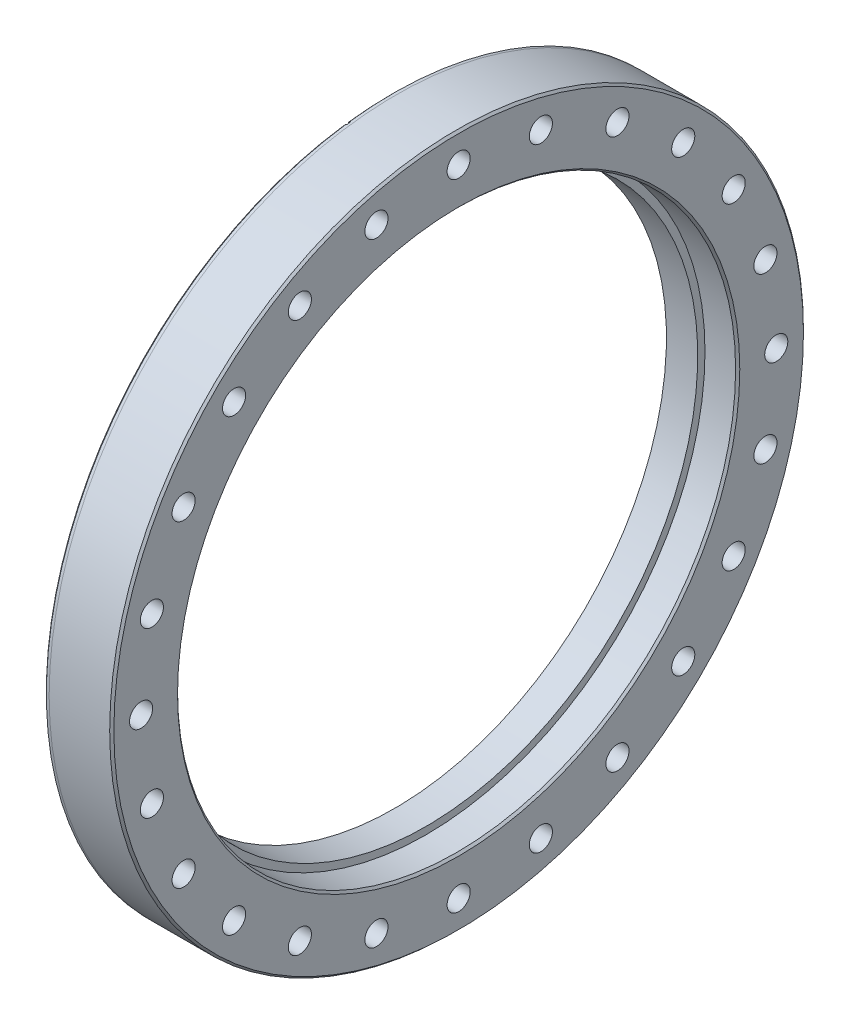
SolidWorks part; units mm, degrees
ref_plane "Front Plane" through (0, 0, 0) normal (0, 0, 1) x (1, 0, 0)
ref_plane "Top Plane" through (0, 0, 0) normal (0, 1, 0) x (1, 0, 0)
ref_plane "Right Plane" through (0, 0, 0) normal (1, 0, 0) x (0, 0, -1)
sketch "Sketch1" plane through (0, 0, 0) normal (0, 0, 1) x (1, 0, 0)
  line L0 (255.9008, 390.4907) -> (255.9008, 381.2451)
  line L1 (267.3308, 383.8867) -> (267.3308, 381.2451)
  line L2 (254.6308, 407.8872) -> (254.6308, 393.1548)
  line L3 (234.5105, 282.0327) -> (295.2534, 282.0327) construction
  line L14 (254.6308, 407.8872) -> (255.3928, 408.6492)
  line L25 (279.2688, 384.6487) -> (278.5068, 383.8867)
  line L27 (256.2619, 393.1577) -> (255.2912, 390.4907)
  line L36 (279.2688, 407.8897) -> (279.2688, 384.6487)
  line L48 (255.9008, 381.2451) -> (267.3308, 381.2451)
  line L49 (278.5068, 383.8867) -> (267.3308, 383.8867)
  line L50 (278.5068, 408.6517) -> (279.2688, 407.8897)
  line L51 (255.9008, 390.4907) -> (255.2912, 390.4907)
  line L52 (255.5972, 393.1577) -> (254.6308, 393.1548)
  line L53 (256.2619, 393.1577) -> (255.5972, 393.1577)
  line L54 (255.3928, 408.6492) -> (256.4093, 408.6517)
  line L55 (256.4093, 408.6517) -> (278.5068, 408.6517)
  dimension "D1" = 126.619
revolve "Revolve1" add sketch "Sketch1" angle 360 about L3
sketch "Sketch2" plane through (254.6308, 0, 0) normal (-1, 0, 0) x (0, 0, 1)
  circle A0 centre (0, 282.0327) radius 115.9256 construction
  point P3 (0, 397.9583)
  dimension "D1" = 231.8512
hole_wizard "Hole1" positions "3DSketch1" profile "Sketch4" legacy end condition through all
sketch3d "3DSketch1"
  point P0 (254.6308, 397.9583, 0)
sketch "Sketch4" plane through (254.6308, 397.9583, 0) normal (0, 1, 0) x (0, 0, 1)
  line L0 (0, 0) -> (0, 24.638)
  line L1 (0, 24.638) -> (4.2164, 24.638)
  line L2 (4.2164, 24.638) -> (4.2164, 0)
  line L3 (4.2164, 0) -> (0, 0)
  line L4 (0, 110) -> (0, -10) construction
  dimension "Diameter" = 8.4328
  dimension "Depth" = 24.638
ref_axis "Axis1" through (267.3308, 282.0327, 0) along (-1, 0, 0)
pattern_circular "CirPattern1" count 24 over 360 about axis through (267.3308, 282.0327, 0) along (-1, 0, 0) of "Hole1"
sketch "Sketch5" plane through (254.6308, 0, 0) normal (-1, 0, 0) x (0, 0, 1)
  line L0 (0, 282.0327) -> (0, 397.9583) construction
  line L1 (0, 282.0327) -> (30.0038, 394.0082) construction
  line L2 (0, 282.0327) -> (17.5047, 414.9942) construction
  line L3 (17.2938, 413.392) -> (18.0807, 413.2884)
  line L4 (18.0807, 413.2884) -> (15.1543, 391.06)
  line L5 (16.5068, 413.4956) -> (13.5804, 391.2672)
  line L6 (17.2938, 413.392) -> (16.5068, 413.4956)
  line L7 (-19.417, 128.4647) -> (-20.9909, 128.6719)
  line L8 (13.5804, 391.2672) -> (15.1543, 391.06)
  line L9 (-13.5588, 172.9625) -> (-19.417, 128.4647)
  line L10 (-15.1327, 173.1697) -> (-20.9909, 128.6719)
  line L11 (-15.1327, 173.1697) -> (-13.5588, 172.9625)
  dimension "D1" = 15
  dimension "D2" = 7.5
  dimension "D3" = 1.5875
extrude "Extrude1" cut sketch "Sketch5" against normal blind 1.016
